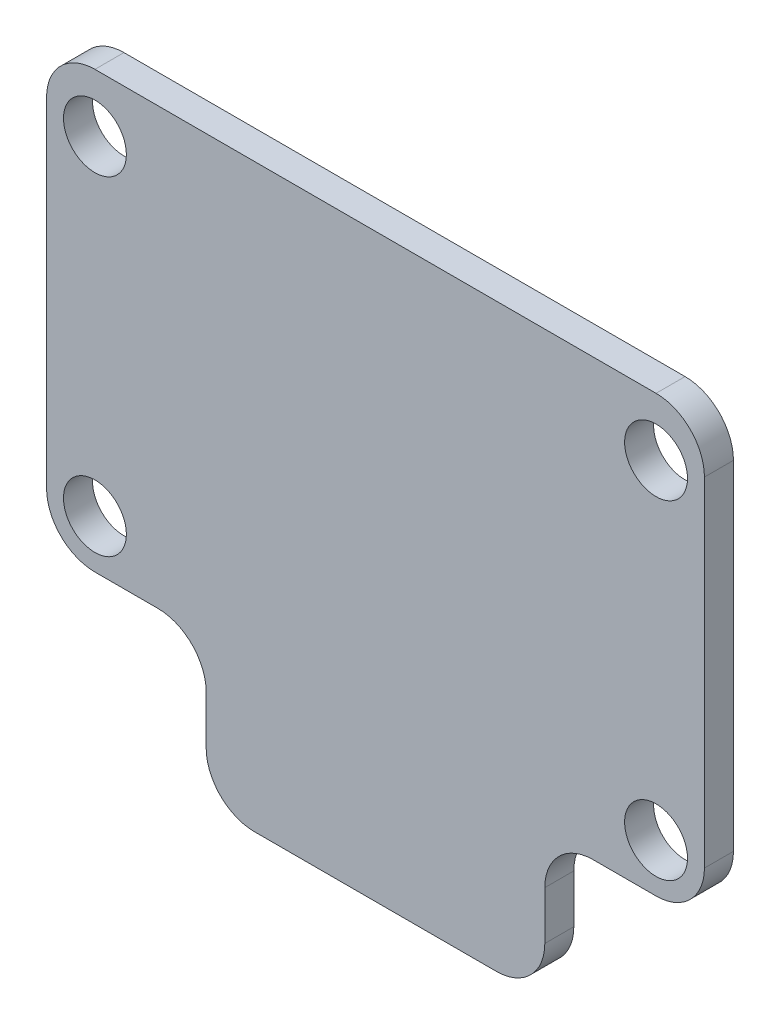
SolidWorks part; units mm, degrees
ref_plane "Plan de face" through (0, 0, 0) normal (0, 0, 1) x (1, 0, 0)
ref_plane "Plan de dessus" through (0, 0, 0) normal (0, 1, 0) x (1, 0, 0)
ref_plane "Plan de droite" through (0, 0, 0) normal (1, 0, 0) x (0, 0, -1)
sketch "Esquisse2" plane through (0, 0, 0) normal (0, 0, 1) x (1, 0, 0)
  line L0 (39.2085, -84.0985) -> (39.2085, -5.0985) construction
  line L1 (107.2085, 1.9015) -> (39.2085, 1.9015)
  line L2 (107.2085, 1.9015) -> (107.2085, -43.0985)
  line L3 (107.2085, -43.0985) -> (90.7085, -43.0985)
  line L4 (39.2085, 1.9015) -> (39.2085, -43.0985)
  line L5 (55.7085, -43.0985) -> (39.2085, -43.0985)
  line L7 (90.7085, -43.0985) -> (90.7085, -58.0985)
  line L8 (90.7085, -58.0985) -> (55.7085, -58.0985)
  line L9 (55.7085, -43.0985) -> (55.7085, -58.0985)
  circle A0 centre (102.2085, -4.0985) radius 3.25
  circle A1 centre (102.2085, -38.0985) radius 3.25
  circle A2 centre (44.2085, -38.0985) radius 3.25
  circle A3 centre (44.2085, -4.0985) radius 3.25
  point P23 (73.2085, -58.0985)
  point P24 (73.2085, 1.9015)
  point P25 (-24.1824, -16.8848)
  dimension "D4" = 6.5
  dimension "D1" = 45
  dimension "D2" = 15
  dimension "D3" = 35
extrude "Boss.-Extru.1" add sketch "Esquisse2" along normal blind 3
fillet "Congé1" radius 5 8 edges at (39.2085, 1.9015, 1.5) (39.2085, -43.0985, 1.5) (55.7085, -58.0985, 1.5) (55.7085, -43.0985, 1.5) (90.7085, -58.0985, 1.5) (90.7085, -43.0985, 1.5) (107.2085, -43.0985, 1.5) (107.2085, 1.9015, 1.5)
